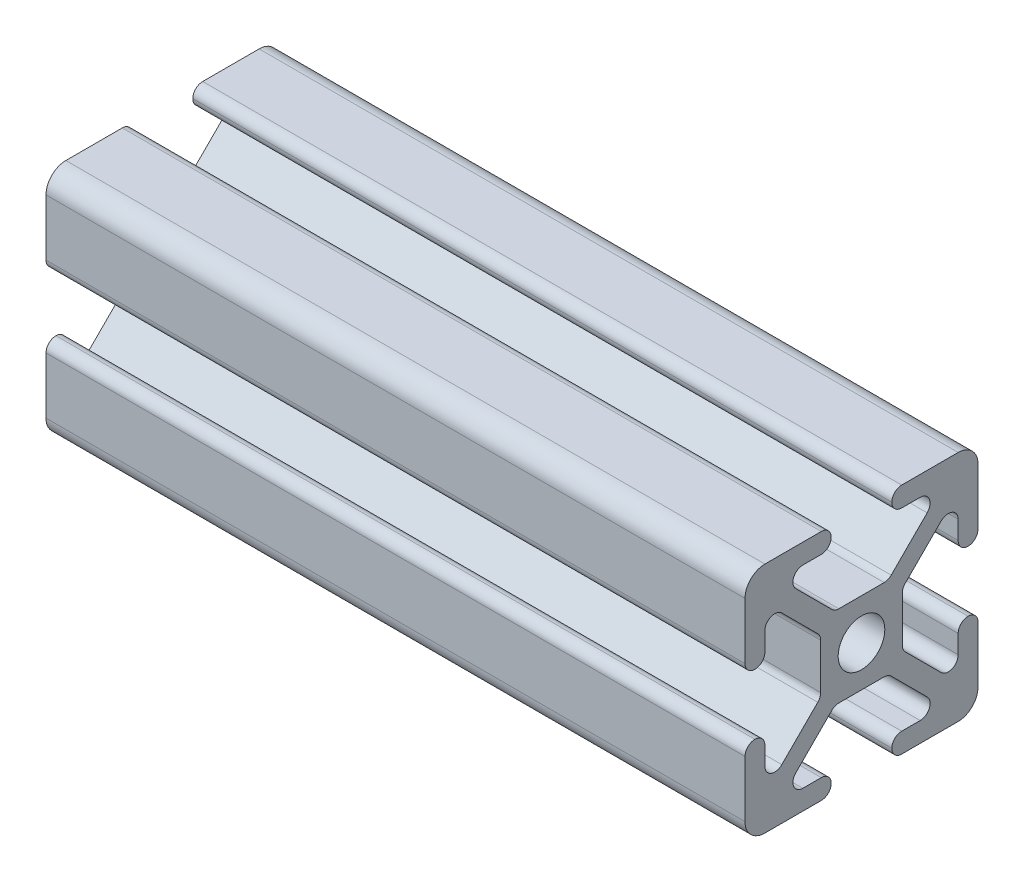
SolidWorks part; units mm, degrees
ref_plane "Front Plane" through (0, 0, 0) normal (1, 0, 0) x (0, 1, 0)
ref_plane "Top Plane" through (0, 0, 0) normal (0, 0, 1) x (0, 1, 0)
ref_plane "Right Plane" through (0, 0, 0) normal (0, 1, 0) x (-1, 0, 0)
sketch "Sketch1" plane through (0, 0, 0) normal (1, 0, 0) x (0, 1, 0)
  line L0 (0, 0) -> (0, 12.5) construction
  line L1 (-12.5, -12.5) -> (12.5, -12.5)
  line L2 (-12.5, -12.5) -> (-12.5, 12.5)
  line L3 (-12.5, 12.5) -> (12.5, 12.5)
  line L4 (12.5, -12.5) -> (12.5, 12.5)
  line L5 (-12.5, -12.5) -> (12.5, 12.5) construction
  line L6 (-12.5, 12.5) -> (12.5, -12.5) construction
  line L7 (-3.25, 12.5) -> (-3.25, 10.37)
  line L8 (-3.25, 10.37) -> (-8.8639, 10.37)
  line L9 (-8.8639, 10.37) -> (-2.8739, 4.38)
  line L10 (-2.8739, 4.38) -> (2.8739, 4.38)
  line L11 (8.8639, 10.37) -> (2.8739, 4.38)
  line L12 (3.25, 10.37) -> (8.8639, 10.37)
  line L13 (3.25, 12.5) -> (3.25, 10.37)
  line L14 (12.5, -3.25) -> (10.37, -3.25)
  line L15 (10.37, -3.25) -> (10.37, -8.8639)
  line L16 (10.37, -8.8639) -> (4.38, -2.8739)
  line L17 (4.38, 2.8739) -> (4.38, -2.8739)
  line L18 (10.37, 8.8639) -> (4.38, 2.8739)
  line L19 (10.37, 3.25) -> (10.37, 8.8639)
  line L20 (12.5, 3.25) -> (10.37, 3.25)
  line L21 (-3.25, -12.5) -> (-3.25, -10.37)
  line L22 (-3.25, -10.37) -> (-8.8639, -10.37)
  line L23 (-8.8639, -10.37) -> (-2.8739, -4.38)
  line L24 (2.8739, -4.38) -> (-2.8739, -4.38)
  line L25 (8.8639, -10.37) -> (2.8739, -4.38)
  line L26 (3.25, -10.37) -> (8.8639, -10.37)
  line L27 (3.25, -12.5) -> (3.25, -10.37)
  line L28 (-12.5, 3.25) -> (-10.37, 3.25)
  line L29 (-10.37, 3.25) -> (-10.37, 8.8639)
  line L30 (-10.37, 8.8639) -> (-4.38, 2.8739)
  line L31 (-4.38, -2.8739) -> (-4.38, 2.8739)
  line L32 (-10.37, -8.8639) -> (-4.38, -2.8739)
  line L33 (-10.37, -3.25) -> (-10.37, -8.8639)
  line L34 (-12.5, -3.25) -> (-10.37, -3.25)
  circle A0 centre (0, 0) radius 2.5
  point P0 (0, 0)
  point P15 (0, 4.38)
  dimension "D3" = 5
  dimension "D1" = 25
  dimension "D2" = 25
  dimension "D4" = 2.13
  dimension "D5" = 2.13
  dimension "D6" = 6.5
  dimension "D7" = 4.38
  dimension "D8" = 4
extrude "Boss-Extrude1" add sketch "Sketch1" along normal blind 75 contours L34 L2 L1 L21 L22 L23 L24 L25 L26 L27 L4 L14 L15 L16 L17 L18 L19 L20 L3 L13 L12 L11 L10 L9 L8 L7 L28 L29 L30 L31 L32 L33 A0 region at (0, -12.1464, -7.875)
fillet "Fillet1" radius 1.065 32 edges at (37.5, -10.37, -8.8639) (37.5, 2.8739, -4.38) (37.5, -2.8739, -4.38) (37.5, -4.38, 2.8739) (37.5, -4.38, -2.8739) (37.5, -2.8739, 4.38) (37.5, 2.8739, 4.38) (37.5, 4.38, 2.8739) (37.5, 4.38, -2.8739) (37.5, -8.8639, -10.37) (37.5, 8.8639, -10.37) (37.5, 10.37, -8.8639) (37.5, -10.37, 8.8639) (37.5, -8.8639, 10.37) (37.5, 10.37, 8.8639) (37.5, 8.8639, 10.37) (37.5, 12.5, 3.25) (37.5, -3.25, -12.5) (37.5, -10.37, 3.25) (37.5, 10.37, 3.25) (37.5, -10.37, -3.25) (37.5, -12.5, -3.25) (37.5, -12.5, 3.25) (37.5, 3.25, -10.37) (37.5, -3.25, -10.37) (37.5, 3.25, -12.5) (37.5, 10.37, -3.25) (37.5, 12.5, -3.25) (37.5, 3.25, 12.5) (37.5, 3.25, 10.37) (37.5, -3.25, 10.37) (37.5, -3.25, 12.5)
fillet "Fillet2" radius 2.13 4 edges at (37.5, 12.5, -12.5) (37.5, -12.5, -12.5) (37.5, 12.5, 12.5) (37.5, -12.5, 12.5)
sketch "Sketch2" plane through (75, 0, 0) normal (1, 0, 0) x (0, 1, 0)
  line L0 (10.37, -12.5) -> (4.315, -12.5)
  line L1 (10.37, -12.5) -> (4.315, -12.5)
  line L2 (4.315, -10.37) -> (6.2927, -10.37)
  line L3 (4.315, -10.37) -> (6.2927, -10.37)
  line L4 (7.0458, -8.5519) -> (3.1858, -4.6919)
  line L5 (7.0458, -8.5519) -> (3.1858, -4.6919)
  line L6 (2.4327, -4.38) -> (-2.4327, -4.38)
  line L7 (2.4327, -4.38) -> (-2.4327, -4.38)
  line L8 (-3.1858, -4.6919) -> (-7.0458, -8.5519)
  line L9 (-3.1858, -4.6919) -> (-7.0458, -8.5519)
  line L10 (-6.2927, -10.37) -> (-4.315, -10.37)
  line L11 (-6.2927, -10.37) -> (-4.315, -10.37)
  line L12 (-4.315, -12.5) -> (-10.37, -12.5)
  line L13 (-4.315, -12.5) -> (-10.37, -12.5)
  line L14 (-12.5, -10.37) -> (-12.5, -4.315)
  line L15 (-12.5, -10.37) -> (-12.5, -4.315)
  line L16 (-10.37, -4.315) -> (-10.37, -6.2927)
  line L17 (-10.37, -4.315) -> (-10.37, -6.2927)
  line L18 (-8.5519, -7.0458) -> (-4.6919, -3.1858)
  line L19 (-8.5519, -7.0458) -> (-4.6919, -3.1858)
  line L20 (-4.38, -2.4327) -> (-4.38, 2.4327)
  line L21 (-4.38, -2.4327) -> (-4.38, 2.4327)
  line L22 (-4.6919, 3.1858) -> (-8.5519, 7.0458)
  line L23 (-4.6919, 3.1858) -> (-8.5519, 7.0458)
  line L24 (-10.37, 6.2927) -> (-10.37, 4.315)
  line L25 (-10.37, 6.2927) -> (-10.37, 4.315)
  line L26 (-12.5, 4.315) -> (-12.5, 10.37)
  line L27 (-12.5, 4.315) -> (-12.5, 10.37)
  line L28 (-10.37, 12.5) -> (-4.315, 12.5)
  line L29 (-10.37, 12.5) -> (-4.315, 12.5)
  line L30 (-4.315, 10.37) -> (-6.2927, 10.37)
  line L31 (-4.315, 10.37) -> (-6.2927, 10.37)
  line L32 (-7.0458, 8.5519) -> (-3.1858, 4.6919)
  line L33 (-7.0458, 8.5519) -> (-3.1858, 4.6919)
  line L34 (-2.4327, 4.38) -> (2.4327, 4.38)
  line L35 (-2.4327, 4.38) -> (2.4327, 4.38)
  line L36 (3.1858, 4.6919) -> (7.0458, 8.5519)
  line L37 (3.1858, 4.6919) -> (7.0458, 8.5519)
  line L38 (6.2927, 10.37) -> (4.315, 10.37)
  line L39 (6.2927, 10.37) -> (4.315, 10.37)
  line L40 (4.315, 12.5) -> (10.37, 12.5)
  line L41 (4.315, 12.5) -> (10.37, 12.5)
  line L42 (12.5, 10.37) -> (12.5, 4.315)
  line L43 (12.5, 10.37) -> (12.5, 4.315)
  line L44 (10.37, 4.315) -> (10.37, 6.2927)
  line L45 (10.37, 4.315) -> (10.37, 6.2927)
  line L46 (8.5519, 7.0458) -> (4.6919, 3.1858)
  line L47 (8.5519, 7.0458) -> (4.6919, 3.1858)
  line L48 (4.38, 2.4327) -> (4.38, -2.4327)
  line L49 (4.38, 2.4327) -> (4.38, -2.4327)
  line L50 (4.6919, -3.1858) -> (8.5519, -7.0458)
  line L51 (4.6919, -3.1858) -> (8.5519, -7.0458)
  line L52 (10.37, -6.2927) -> (10.37, -4.315)
  line L53 (10.37, -6.2927) -> (10.37, -4.315)
  line L54 (12.5, -4.315) -> (12.5, -10.37)
  line L55 (12.5, -4.315) -> (12.5, -10.37)
  arc A0 (10.37, -12.5) -> (12.5, -10.37) centre (10.37, -10.37) ccw
  circle A1 centre (0, 0) radius 2.5
  circle A2 centre (0, 0) radius 2.5
  arc A3 (10.37, -12.5) -> (12.5, -10.37) centre (10.37, -10.37) ccw
  arc A4 (3.25, -11.435) -> (4.315, -12.5) centre (4.315, -11.435) ccw
  arc A5 (3.25, -11.435) -> (4.315, -12.5) centre (4.315, -11.435) ccw
  arc A6 (4.315, -10.37) -> (3.25, -11.435) centre (4.315, -11.435) ccw
  arc A7 (4.315, -10.37) -> (3.25, -11.435) centre (4.315, -11.435) ccw
  arc A8 (6.2927, -10.37) -> (7.0458, -8.5519) centre (6.2927, -9.305) ccw
  arc A9 (6.2927, -10.37) -> (7.0458, -8.5519) centre (6.2927, -9.305) ccw
  arc A10 (3.1858, -4.6919) -> (2.4327, -4.38) centre (2.4327, -5.445) ccw
  arc A11 (3.1858, -4.6919) -> (2.4327, -4.38) centre (2.4327, -5.445) ccw
  arc A12 (-2.4327, -4.38) -> (-3.1858, -4.6919) centre (-2.4327, -5.445) ccw
  arc A13 (-2.4327, -4.38) -> (-3.1858, -4.6919) centre (-2.4327, -5.445) ccw
  arc A14 (-7.0458, -8.5519) -> (-6.2927, -10.37) centre (-6.2927, -9.305) ccw
  arc A15 (-7.0458, -8.5519) -> (-6.2927, -10.37) centre (-6.2927, -9.305) ccw
  arc A16 (-3.25, -11.435) -> (-4.315, -10.37) centre (-4.315, -11.435) ccw
  arc A17 (-3.25, -11.435) -> (-4.315, -10.37) centre (-4.315, -11.435) ccw
  arc A18 (-4.315, -12.5) -> (-3.25, -11.435) centre (-4.315, -11.435) ccw
  arc A19 (-4.315, -12.5) -> (-3.25, -11.435) centre (-4.315, -11.435) ccw
  arc A20 (-12.5, -10.37) -> (-10.37, -12.5) centre (-10.37, -10.37) ccw
  arc A21 (-12.5, -10.37) -> (-10.37, -12.5) centre (-10.37, -10.37) ccw
  arc A22 (-11.435, -3.25) -> (-12.5, -4.315) centre (-11.435, -4.315) ccw
  arc A23 (-11.435, -3.25) -> (-12.5, -4.315) centre (-11.435, -4.315) ccw
  arc A24 (-10.37, -4.315) -> (-11.435, -3.25) centre (-11.435, -4.315) ccw
  arc A25 (-10.37, -4.315) -> (-11.435, -3.25) centre (-11.435, -4.315) ccw
  arc A26 (-10.37, -6.2927) -> (-8.5519, -7.0458) centre (-9.305, -6.2927) ccw
  arc A27 (-10.37, -6.2927) -> (-8.5519, -7.0458) centre (-9.305, -6.2927) ccw
  arc A28 (-4.6919, -3.1858) -> (-4.38, -2.4327) centre (-5.445, -2.4327) ccw
  arc A29 (-4.6919, -3.1858) -> (-4.38, -2.4327) centre (-5.445, -2.4327) ccw
  arc A30 (-4.38, 2.4327) -> (-4.6919, 3.1858) centre (-5.445, 2.4327) ccw
  arc A31 (-4.38, 2.4327) -> (-4.6919, 3.1858) centre (-5.445, 2.4327) ccw
  arc A32 (-8.5519, 7.0458) -> (-10.37, 6.2927) centre (-9.305, 6.2927) ccw
  arc A33 (-8.5519, 7.0458) -> (-10.37, 6.2927) centre (-9.305, 6.2927) ccw
  arc A34 (-11.435, 3.25) -> (-10.37, 4.315) centre (-11.435, 4.315) ccw
  arc A35 (-11.435, 3.25) -> (-10.37, 4.315) centre (-11.435, 4.315) ccw
  arc A36 (-12.5, 4.315) -> (-11.435, 3.25) centre (-11.435, 4.315) ccw
  arc A37 (-12.5, 4.315) -> (-11.435, 3.25) centre (-11.435, 4.315) ccw
  arc A38 (-10.37, 12.5) -> (-12.5, 10.37) centre (-10.37, 10.37) ccw
  arc A39 (-10.37, 12.5) -> (-12.5, 10.37) centre (-10.37, 10.37) ccw
  arc A40 (-3.25, 11.435) -> (-4.315, 12.5) centre (-4.315, 11.435) ccw
  arc A41 (-3.25, 11.435) -> (-4.315, 12.5) centre (-4.315, 11.435) ccw
  arc A42 (-4.315, 10.37) -> (-3.25, 11.435) centre (-4.315, 11.435) ccw
  arc A43 (-4.315, 10.37) -> (-3.25, 11.435) centre (-4.315, 11.435) ccw
  arc A44 (-6.2927, 10.37) -> (-7.0458, 8.5519) centre (-6.2927, 9.305) ccw
  arc A45 (-6.2927, 10.37) -> (-7.0458, 8.5519) centre (-6.2927, 9.305) ccw
  arc A46 (-3.1858, 4.6919) -> (-2.4327, 4.38) centre (-2.4327, 5.445) ccw
  arc A47 (-3.1858, 4.6919) -> (-2.4327, 4.38) centre (-2.4327, 5.445) ccw
  arc A48 (2.4327, 4.38) -> (3.1858, 4.6919) centre (2.4327, 5.445) ccw
  arc A49 (2.4327, 4.38) -> (3.1858, 4.6919) centre (2.4327, 5.445) ccw
  arc A50 (7.0458, 8.5519) -> (6.2927, 10.37) centre (6.2927, 9.305) ccw
  arc A51 (7.0458, 8.5519) -> (6.2927, 10.37) centre (6.2927, 9.305) ccw
  arc A52 (3.25, 11.435) -> (4.315, 10.37) centre (4.315, 11.435) ccw
  arc A53 (3.25, 11.435) -> (4.315, 10.37) centre (4.315, 11.435) ccw
  arc A54 (4.315, 12.5) -> (3.25, 11.435) centre (4.315, 11.435) ccw
  arc A55 (4.315, 12.5) -> (3.25, 11.435) centre (4.315, 11.435) ccw
  arc A56 (12.5, 10.37) -> (10.37, 12.5) centre (10.37, 10.37) ccw
  arc A57 (12.5, 10.37) -> (10.37, 12.5) centre (10.37, 10.37) ccw
  arc A58 (11.435, 3.25) -> (12.5, 4.315) centre (11.435, 4.315) ccw
  arc A59 (11.435, 3.25) -> (12.5, 4.315) centre (11.435, 4.315) ccw
  arc A60 (10.37, 4.315) -> (11.435, 3.25) centre (11.435, 4.315) ccw
  arc A61 (10.37, 4.315) -> (11.435, 3.25) centre (11.435, 4.315) ccw
  arc A62 (10.37, 6.2927) -> (8.5519, 7.0458) centre (9.305, 6.2927) ccw
  arc A63 (10.37, 6.2927) -> (8.5519, 7.0458) centre (9.305, 6.2927) ccw
  arc A64 (4.6919, 3.1858) -> (4.38, 2.4327) centre (5.445, 2.4327) ccw
  arc A65 (4.6919, 3.1858) -> (4.38, 2.4327) centre (5.445, 2.4327) ccw
  arc A66 (4.38, -2.4327) -> (4.6919, -3.1858) centre (5.445, -2.4327) ccw
  arc A67 (4.38, -2.4327) -> (4.6919, -3.1858) centre (5.445, -2.4327) ccw
  arc A68 (8.5519, -7.0458) -> (10.37, -6.2927) centre (9.305, -6.2927) ccw
  arc A69 (8.5519, -7.0458) -> (10.37, -6.2927) centre (9.305, -6.2927) ccw
  arc A70 (11.435, -3.25) -> (10.37, -4.315) centre (11.435, -4.315) ccw
  arc A71 (11.435, -3.25) -> (10.37, -4.315) centre (11.435, -4.315) ccw
  arc A72 (12.5, -4.315) -> (11.435, -3.25) centre (11.435, -4.315) ccw
  arc A73 (12.5, -4.315) -> (11.435, -3.25) centre (11.435, -4.315) ccw
  dimension "D1" = 0
